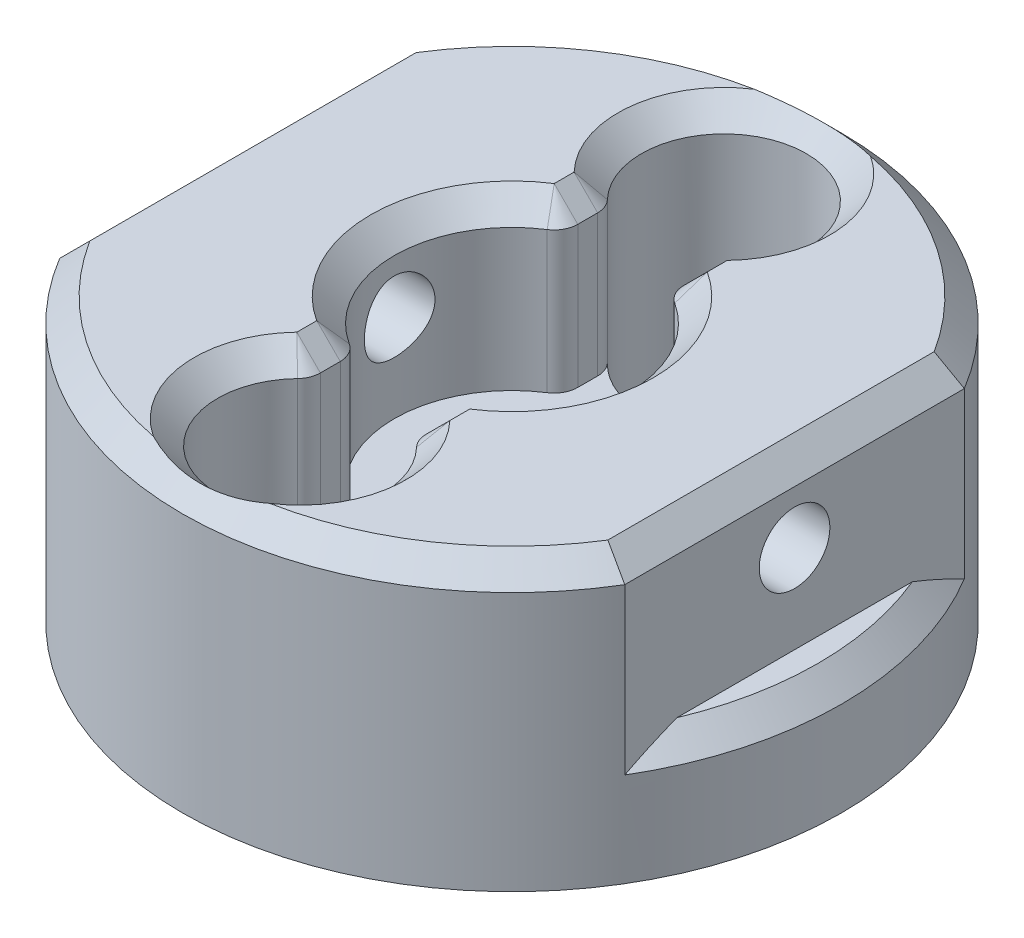
SolidWorks part; units mm, degrees
ref_plane "Front Plane" through (0, 0, 0) normal (0, 0, 1) x (1, 0, 0)
ref_plane "Top Plane" through (0, 0, 0) normal (0, 1, 0) x (1, 0, 0)
ref_plane "Right Plane" through (0, 0, 0) normal (1, 0, 0) x (0, 0, -1)
sketch "Sketch1" plane through (0, 0, 0) normal (0, 1, 0) x (1, 0, 0)
  circle A0 centre (0, 0) radius 14
  circle A1 centre (0, 0) radius 2.25
  dimension "D1" = 28
  dimension "D2" = 4.5
extrude "Boss-Extrude1" add sketch "Sketch1" along normal blind 5
sketch "Sketch2" plane through (0, 5, 0) normal (0, 1, 0) x (1, 0, 0)
  line L0 (0, -1000) -> (0, 49000) construction
  line L1 (-1000, 0) -> (49000, 0) construction
  line L2 (4.2426, 4.2426) -> (0, 0) construction
  circle A0 centre (0, 9) radius 1.5
  circle A1 centre (4.2426, 4.2426) radius 1.5 construction
  dimension "D1" = 3
  dimension "D2" = 3
  dimension "D3" = 9
  dimension "D4" = 6
  dimension "D5" = 45
extrude "Cut-Extrude1" cut sketch "Sketch2" against normal through all
sketch "Sketch4" plane through (0, 5, 0) normal (0, 1, 0) x (1, 0, 0)
  circle A0 centre (0, 9) radius 3.5
  dimension "D1" = 7
extrude "Cut-Extrude2" cut sketch "Sketch4" against normal blind 3
pattern_circular "CirPattern1" count 2 over 360 about axis through (0, 5, 0) along (0, -1, 0) of "Cut-Extrude1", "Cut-Extrude2" reverse direction yes
sketch "Sketch5" plane through (0, 5, 0) normal (0, 1, 0) x (1, 0, 0)
  circle A0 centre (0, 0) radius 5
  circle A1 centre (0, 0) radius 14
  circle A2 centre (0, 0) radius 14 construction
  dimension "D1" = 10
extrude "Boss-Extrude2" add sketch "Sketch5" along normal blind 7
sketch "Sketch6" plane through (0, 5, 0) normal (0, 1, 0) x (1, 0, 0)
  circle A2 centre (0, 9) radius 3.5 construction
  circle A3 centre (0, -9) radius 3.5 construction
  circle A6 centre (0, 9) radius 3.5
  circle A7 centre (0, -9) radius 3.5
extrude "Cut-Extrude3" cut sketch "Sketch6" along normal through all
sketch "Sketch9" plane through (0, 12, 0) normal (0, 1, 0) x (1, 0, 0)
  line L1 (12, -15) -> (-12, -15)
  line L2 (12, -15) -> (12, 15)
  line L3 (12, 15) -> (-12, 15)
  line L4 (-12, -15) -> (-12, 15)
  line L5 (12, -15) -> (-12, 15) construction
  line L6 (12, 15) -> (-12, -15) construction
  point P0 (0, 0)
  dimension "D1" = 12
  dimension "D2" = 30
extrude "Cut-Extrude5" cut sketch "Sketch9" against normal up to surface (7 mm away) flip side to cut up to face at (0, 5, 2.25)
ref_axis "Axis1" through (0, 12, 0) along (0, -1, 0)
sketch "Sketch10" plane through (12, 0, 0) normal (1, 0, 0) x (0, 0, -1)
  line L0 (7.2111, 5) -> (-7.2111, 5) construction
  circle A0 centre (0, 8.75) radius 1.5
  dimension "D2" = 3
  dimension "D1" = 3.75
extrude "Cut-Extrude6" cut sketch "Sketch10" against normal through all
sketch "Sketch12" plane through (0, 12, 0) normal (0, 1, 0) x (1, 0, 0)
  line L1 (2.25, -9) -> (-2.25, -9)
  line L2 (2.25, -9) -> (2.25, 9)
  line L3 (2.25, 9) -> (-2.25, 9)
  line L4 (-2.25, -9) -> (-2.25, 9)
  line L5 (2.25, -9) -> (-2.25, 9) construction
  line L6 (2.25, 9) -> (-2.25, -9) construction
  circle A0 centre (0, 0) radius 2.25 construction
  point P0 (0, 0)
  point P6 (0, 9)
extrude "Cut-Extrude7" cut sketch "Sketch12" against normal up to surface (7 mm away) up to face at (0, 5, 2.25)
chamfer "Chamfer2" distance 0.4 angle 85 1 edges at (0, 5, 2.25) first distance on face at (0, 5, 2.25)
fillet "Fillet2" radius 1 8 edges at (2.25, 8.5, 6.319) (2.25, 8.5, 4.4651) (2.25, 8.5, -4.4651) (2.25, 8.5, -6.319) (-2.25, 8.5, -6.319) (-2.25, 8.5, -4.4651) (-2.25, 8.5, 4.4651) (-2.25, 8.5, 6.319)
chamfer "Chamfer3" distance 1 angle 45 22 edges at (-14, 5, 0) (14, 5, 0) (12, 12, 0) (0, 12, -14) (-12, 12, 0) (0, 12, 14) (5, 12, 0) (2.372, 12, -4.5648) (2.372, 12, 4.5648) (2.25, 12, -5.4655) (2.25, 12, 5.4655) (2.322, 12, -6.2602) (2.322, 12, 6.2602) (0, 12, -12.5) (0, 12, 12.5) (-2.322, 12, -6.2602) (-2.322, 12, 6.2602) (-2.25, 12, -5.4655) (-2.25, 12, 5.4655) (-2.372, 12, -4.5648) (-2.372, 12, 4.5648) (-5, 12, 0)
